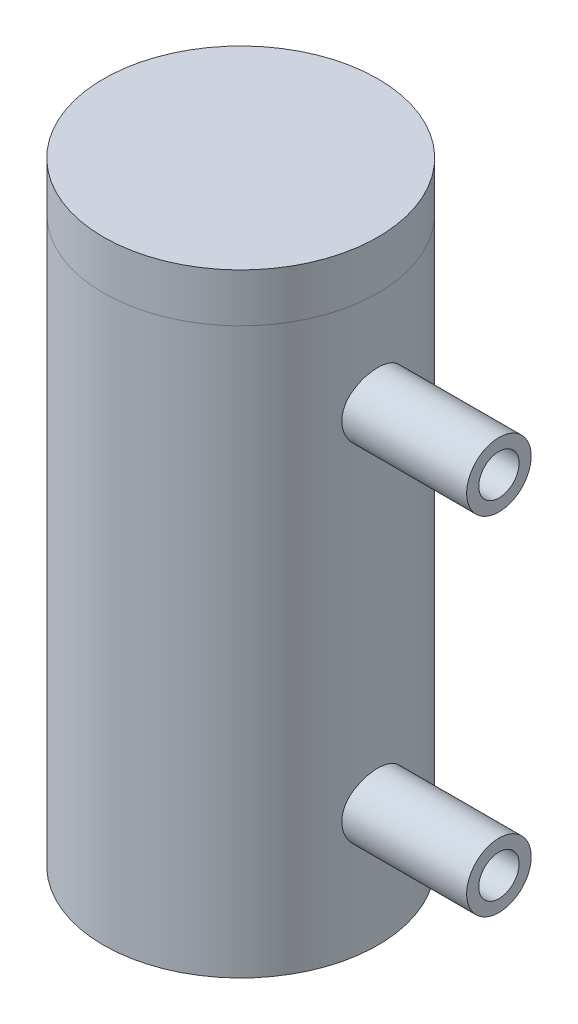
SolidWorks part; units mm, degrees
ref_plane "Front Plane" through (0, 0, 0) normal (0, 0, 1) x (1, 0, 0)
ref_plane "Top Plane" through (0, 0, 0) normal (0, 1, 0) x (1, 0, 0)
ref_plane "Right Plane" through (0, 0, 0) normal (1, 0, 0) x (0, 0, -1)
other "Configuration Table"
sketch "Sketch1" plane through (0, 0, 0) normal (0, 1, 0) x (1, 0, 0)
  circle A0 centre (29, -498) radius 17
extrude "sleeve" add sketch "Sketch1" along normal blind 70 from offset 410 separate body
sketch "Sketch2" plane through (0, 0, 0) normal (0, 1, 0) x (1, 0, 0)
  circle A0 centre (29, -498) radius 15
extrude "bore" add sketch "Sketch2" along normal blind 72 from offset 409 separate body
combine bodies "Combine1" operation type subtract main body 102 bodies to subtract 103
sketch "Sketch3" plane through (0, 0, 0) normal (0, 1, 0) x (1, 0, 0)
  circle A0 centre (29, -498) radius 17
extrude "cap" add sketch "Sketch3" along normal blind 6 from offset 480 separate body
sketch "Sketch4" plane through (0, 0, 0) normal (1, 0, 0) x (0, 0, -1)
  circle A0 centre (-498, 425) radius 4
extrude "spigot_425" add sketch "Sketch4" along normal blind 16.5 from offset 44.5 separate body
sketch "Sketch5" plane through (0, 0, 0) normal (1, 0, 0) x (0, 0, -1)
  circle A0 centre (-498, 425) radius 2.5
extrude "spigot_bore" add sketch "Sketch5" along normal blind 18 from offset 44 separate body
combine bodies "Combine2" operation type subtract main body 106 bodies to subtract 107
sketch "Sketch6" plane through (0, 0, 0) normal (1, 0, 0) x (0, 0, -1)
  circle A0 centre (-498, 468) radius 4
extrude "spigot_468" add sketch "Sketch6" along normal blind 16.5 from offset 44.5 separate body
sketch "Sketch7" plane through (0, 0, 0) normal (1, 0, 0) x (0, 0, -1)
  circle A0 centre (-498, 468) radius 2.5
extrude "Boss-Extrude7" add sketch "Sketch7" along normal blind 18 from offset 44 separate body
combine bodies "Combine3" operation type subtract main body 109 bodies to subtract 110
